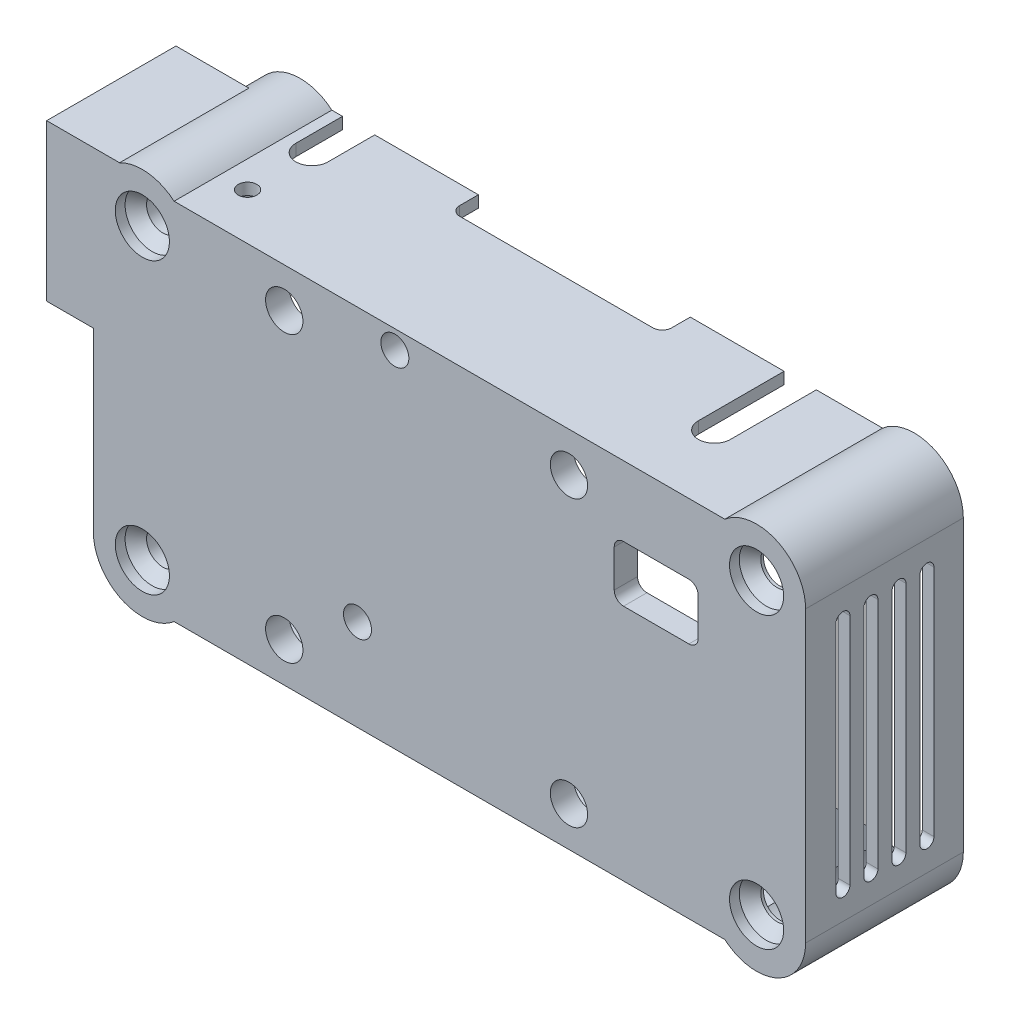
SolidWorks part; units mm, degrees
ref_plane "Front Plane" through (0, 0, 0) normal (0, 0, 1) x (1, 0, 0)
ref_plane "Top Plane" through (0, 0, 0) normal (0, 1, 0) x (1, 0, 0)
ref_plane "Right Plane" through (0, 0, 0) normal (1, 0, 0) x (0, 0, -1)
sketch "Sketch1" plane through (0, 0, 0) normal (0, 0, 1) x (1, 0, 0)
  line L0 (-29.7106, 19.8451) -> (30.4992, 19.8451)
  line L1 (-36.2557, 17.3451) -> (-36.2557, -13.6549)
  line L2 (-29.7106, -16.1549) -> (30.4992, -16.1549)
  line L3 (37.0443, 17.3451) -> (37.0443, -13.6549)
  circle A1 centre (-32.5057, 17.3451) radius 3.75
  arc A2 (-29.7106, 19.8451) -> (-36.2557, 17.3451) centre (-32.5057, 17.3451) ccw construction
  circle A3 centre (-32.5057, 17.3451) radius 1.75
  circle A4 centre (-32.5057, 17.3451) radius 1.75 construction
  circle A8 centre (-32.5057, -13.6549) radius 1.75
  circle A9 centre (-32.5057, -13.6549) radius 1.75 construction
  circle A10 centre (-32.5057, -13.6549) radius 3.75
  arc A11 (-36.2557, -13.6549) -> (-29.7106, -16.1549) centre (-32.5057, -13.6549) ccw construction
  circle A12 centre (33.2943, 17.3451) radius 3.75
  circle A14 centre (33.2943, 17.3451) radius 1.75
  circle A16 centre (33.2943, -13.6549) radius 3.75
  circle A18 centre (33.2943, -13.6549) radius 1.75
  circle A20 centre (33.2943, -13.6549) radius 1.75 construction
  circle A21 centre (33.2943, 17.3451) radius 1.75 construction
  arc A22 (37.0443, 17.3451) -> (30.1222, 15.3451) centre (33.2943, 17.3451) ccw construction
extrude "Boss-Extrude1" add sketch "Sketch1" along normal blind 2.5 contours A16 L3 A12 L0 A1 L1 A10 L2 | A1 A3 | A10 A8 | A12 A14 | A16 A18 region at (0.3943, 1.8451, 0) region at (-29.1016, 18.6453, 0) region at (34.5945, 20.7492, 0) region at (-32.5057, -10.011, 0) region at (34.5945, -17.059, 0)
sketch "Sketch2" plane through (0, 0, 2.5) normal (0, 0, 1) x (1, 0, 0)
  line L0 (-37.7557, 17.3451) -> (-37.7557, -13.6549)
  line L1 (-29.1053, -17.6549) -> (29.8939, -17.6549)
  line L2 (38.5443, -13.6549) -> (38.5443, 17.3451)
  line L3 (29.8939, 21.3451) -> (-29.1053, 21.3451)
  line L4 (-29.7106, -16.1549) -> (30.4992, -16.1549)
  line L5 (37.0443, -13.6549) -> (37.0443, 17.3451)
  line L6 (30.4992, 19.8451) -> (-29.7106, 19.8451)
  line L7 (-36.2557, 17.3451) -> (-36.2557, -13.6549)
  line L8 (-29.7106, -16.1549) -> (30.4992, -16.1549)
  line L9 (37.0443, -13.6549) -> (37.0443, 17.3451)
  line L10 (30.4992, 19.8451) -> (-29.7106, 19.8451)
  line L11 (-36.2557, 17.3451) -> (-36.2557, -13.6549)
  arc A0 (-29.1053, 21.3451) -> (-37.7557, 17.3451) centre (-32.5057, 17.3451) ccw
  arc A1 (-37.7557, -13.6549) -> (-29.1053, -17.6549) centre (-32.5057, -13.6549) ccw
  arc A2 (29.8939, -17.6549) -> (38.5443, -13.6549) centre (33.2943, -13.6549) ccw
  arc A3 (38.5443, 17.3451) -> (29.8939, 21.3451) centre (33.2943, 17.3451) ccw
  arc A4 (30.4992, -16.1549) -> (37.0443, -13.6549) centre (33.2943, -13.6549) ccw
  arc A5 (37.0443, 17.3451) -> (30.4992, 19.8451) centre (33.2943, 17.3451) ccw
  arc A6 (-29.7106, 19.8451) -> (-36.2557, 17.3451) centre (-32.5057, 17.3451) ccw
  arc A7 (-36.2557, -13.6549) -> (-29.7106, -16.1549) centre (-32.5057, -13.6549) ccw
  arc A8 (30.4992, -16.1549) -> (37.0443, -13.6549) centre (33.2943, -13.6549) ccw
  arc A9 (37.0443, 17.3451) -> (30.4992, 19.8451) centre (33.2943, 17.3451) ccw
  arc A10 (-29.7106, 19.8451) -> (-36.2557, 17.3451) centre (-32.5057, 17.3451) ccw
  arc A11 (-36.2557, -13.6549) -> (-29.7106, -16.1549) centre (-32.5057, -13.6549) ccw
  dimension "D1" = 0
  dimension "D2" = 1.5
extrude "Boss-Extrude2" add sketch "Sketch2" against normal up to surface (2.5 mm away) up to face at (0.3943, 1.8451, 0)
sketch "Sketch3" plane through (0, 0, 0) normal (0, 0, -1) x (-1, 0, 0)
  line L1 (29.601, 20.0951) -> (-30.3896, 20.0951)
  line L2 (-37.2943, 17.3451) -> (-37.2943, -13.6549)
  line L3 (-30.3896, -16.4049) -> (29.601, -16.4049)
  line L4 (29.1053, 21.3451) -> (-29.8939, 21.3451)
  line L5 (-38.5443, 17.3451) -> (-38.5443, -13.6549)
  line L6 (-29.8939, -17.6549) -> (29.1053, -17.6549)
  line L7 (37.7557, -13.6549) -> (37.7557, 17.3451)
  line L8 (29.1053, 21.3451) -> (-29.8939, 21.3451)
  line L9 (-38.5443, 17.3451) -> (-38.5443, -13.6549)
  line L10 (-29.8939, -17.6549) -> (29.1053, -17.6549)
  line L11 (37.7557, -13.6549) -> (37.7557, 17.3451)
  line L12 (36.5057, -13.6549) -> (36.5057, 17.3451)
  arc A1 (-30.3896, 20.0951) -> (-37.2943, 17.3451) centre (-33.2943, 17.3451) ccw
  arc A2 (-37.2943, -13.6549) -> (-30.3896, -16.4049) centre (-33.2943, -13.6549) ccw
  arc A3 (29.601, -16.4049) -> (36.5057, -13.6549) centre (32.5057, -13.6549) ccw
  arc A4 (37.7557, 17.3451) -> (29.1053, 21.3451) centre (32.5057, 17.3451) ccw
  arc A5 (-29.8939, 21.3451) -> (-38.5443, 17.3451) centre (-33.2943, 17.3451) ccw
  arc A6 (-38.5443, -13.6549) -> (-29.8939, -17.6549) centre (-33.2943, -13.6549) ccw
  arc A7 (29.1053, -17.6549) -> (37.7557, -13.6549) centre (32.5057, -13.6549) ccw
  arc A8 (37.7557, 17.3451) -> (29.1053, 21.3451) centre (32.5057, 17.3451) ccw
  arc A9 (-29.8939, 21.3451) -> (-38.5443, 17.3451) centre (-33.2943, 17.3451) ccw
  arc A10 (-38.5443, -13.6549) -> (-29.8939, -17.6549) centre (-33.2943, -13.6549) ccw
  arc A11 (29.1053, -17.6549) -> (37.7557, -13.6549) centre (32.5057, -13.6549) ccw
  arc A12 (36.5057, 17.3451) -> (29.601, 20.0951) centre (32.5057, 17.3451) ccw
  dimension "D1" = 0
  dimension "D2" = 1.25
extrude "Boss-Extrude3" add sketch "Sketch3" along normal up to surface (14.4 mm away)
sketch "Sketch8" plane through (0, 0, 0) normal (0, 0, -1) x (-1, 0, 0)
  line L0 (37.7557, 17.3451) -> (37.7557, -13.6549)
  line L1 (29.1053, 21.3451) -> (29.1053, -17.6549)
  circle A0 centre (32.5057, 17.3451) radius 5.25
  arc A1 (37.7557, 17.3451) -> (29.1053, 21.3451) centre (32.5057, 17.3451) ccw construction
  circle A2 centre (32.5057, 17.3451) radius 1.75
  circle A3 centre (32.5057, 17.3451) radius 1.75 construction
  circle A4 centre (32.5057, -13.6549) radius 5.25
  arc A5 (29.1053, -17.6549) -> (37.7557, -13.6549) centre (32.5057, -13.6549) ccw construction
  circle A6 centre (32.5057, -13.6549) radius 1.75
  circle A7 centre (32.5057, -13.6549) radius 1.75 construction
  circle M3 centre (32.5057, 17.3451) radius 1.75
  circle M4 centre (32.5057, -13.6549) radius 1.75
  arc M5 (29.601, -16.4049) -> (36.5057, -13.6549) centre (32.5057, -13.6549) ccw
  line M6 (36.5057, -13.6549) -> (36.5057, 17.3451)
  arc M7 (36.5057, 17.3451) -> (29.601, 20.0951) centre (32.5057, 17.3451) ccw
  line M8 (29.601, 20.0951) -> (-30.3896, 20.0951)
  line M12 (-30.3896, -16.4049) -> (29.601, -16.4049)
extrude "Boss-Extrude4" add sketch "Sketch8" along normal up to surface (6.75 mm away) contours L1 A0 M6 M7 M8 M3 | A4 A0 L1 M6 | A4 L1 M6 M12 M5 M4 region at (-32.835, 1.8451, 0) region at (-32.9201, 12.2303, 0) region at (-36.3872, -11.9547, 0)
sketch "Sketch4" plane through (-37.7557, 0, 0) normal (-1, 0, 0) x (0, 0, 1)
  line L12 (-11.9, -11.8549) -> (-3.3, -11.8549)
  line L13 (-3.3, -11.8549) -> (-3.3, 1.2216)
  line L14 (-3.3, 1.2216) -> (-6.0107, 4.2451)
  line L15 (-6.0107, 4.2451) -> (-9.1893, 4.2451)
  line L16 (-9.1893, 4.2451) -> (-11.9, 1.2216)
  line L17 (-11.9, 1.2216) -> (-11.9, -11.8549)
  line L18 (-11.9, -11.8549) -> (-3.3, -11.8549)
  line L19 (-3.3, -11.8549) -> (-3.3, 1.2216)
  line L20 (-3.3, 1.2216) -> (-6.0107, 4.2451)
  line L21 (-6.0107, 4.2451) -> (-9.1893, 4.2451)
  line L22 (-9.1893, 4.2451) -> (-11.9, 1.2216)
  line L23 (-11.9, 1.2216) -> (-11.9, -11.8549)
  dimension "D1" = 0.2
extrude "Cut-Extrude1" cut sketch "Sketch4" against normal up to next
sketch "Sketch5" plane through (0, 21.3451, 0) normal (0, 1, 0) x (1, 0, 0)
  line L0 (-27.9607, 9.4) -> (-27.9607, 14.4)
  line L1 (-29.1053, 14.4) -> (29.8939, 14.4) construction
  line L2 (-24.5107, 9.4) -> (-24.5107, 14.4)
  line L3 (-24.5107, 14.4) -> (-27.9607, 14.4)
  line L4 (19.3445, 5.2047) -> (19.3445, 14.4)
  line L5 (22.7945, 5.2047) -> (22.7945, 14.4)
  circle A1 centre (21.0695, 5.2047) radius 1.725
  circle A2 centre (-26.2357, 9.4) radius 1.725
  circle A3 centre (-26.2357, 9.4) radius 1.725
  circle A4 centre (21.0695, 5.2047) radius 0.95 construction
  line M3 (29.8939, 14.4) -> (-29.1053, 14.4)
  dimension "D1" = 0.5
extrude "Cut-Extrude2" cut sketch "Sketch5" against normal up to next contours A3 | A3 L2 L0 M3 | A1 L5 L4 M3 | A1 region at (21.0695, 21.3451, -10.4703) region at (-26.2357, 21.3451, -12.5571) region at (-26.2357, 21.3451, -9.4) region at (21.0695, 21.3451, -5.2047)
sketch "Sketch6" plane through (0, 21.3451, 0) normal (0, 1, 0) x (1, 0, 0)
  line L0 (-26.2357, 7.675) -> (-26.2357, -2.5) construction
  line L1 (29.8939, -2.5) -> (-29.1053, -2.5) construction
  arc A0 (-27.9607, 9.4) -> (-24.5107, 9.4) centre (-26.2357, 9.4) ccw construction
  circle A1 centre (-26.2357, 2.5) radius 1
  dimension "D1" = 2
  dimension "D2" = 5
extrude "Cut-Extrude3" cut sketch "Sketch6" against normal through all
sketch "Sketch7" plane through (0, 0, 2.5) normal (0, 0, 1) x (1, 0, 0)
  line L1 (27.0443, 7.8451) -> (18.0443, 7.8451)
  line L2 (27.0443, 7.8451) -> (27.0443, 13.8451)
  line L3 (27.0443, 13.8451) -> (18.0443, 13.8451)
  line L4 (18.0443, 7.8451) -> (18.0443, 13.8451)
  line L6 (38.5443, -13.6549) -> (38.5443, 17.3451) construction
  line L7 (29.8939, 21.3451) -> (-29.1053, 21.3451) construction
  line L8 (-3.2057, 19.3451) -> (-3.2057, 21.3451) construction
  line L9 (-7.7057, 19.3451) -> (-7.7057, 21.3451) construction
  line L10 (-3.2057, 18.0451) -> (-3.2057, 19.8451) construction
  line L11 (-7.7057, 18.0451) -> (-7.7057, 19.8451) construction
  circle A0 centre (-9.4557, -7.8549) radius 1.5
  circle A1 centre (-5.4557, 19.3451) radius 2.25
  circle A2 centre (-9.4557, -7.8549) radius 0.875 construction
  circle A3 centre (-5.4557, 19.3451) radius 1.5
  dimension "D5" = 2
  dimension "D6" = 3
  dimension "D1" = 11.5
  dimension "D2" = 7.5
  dimension "D3" = 6
  dimension "D4" = 9
extrude "Cut-Extrude4" cut sketch "Sketch7" against normal up to next contours L4 L1 L2 L3 | A3 | A0 region at (22.5443, 10.8451, 2.5) region at (-9.4557, -7.8549, 2.5) region at (-5.4557, 19.3451, 2.5)
sketch "Sketch9" plane through (0, 0, 2.5) normal (0, 0, 1) x (1, 0, 0)
  circle A0 centre (-32.5057, 17.3451) radius 2.9
  circle A1 centre (33.2943, 17.3451) radius 2.9
  circle A2 centre (33.2943, -13.6549) radius 2.9
  circle A3 centre (-32.5057, -13.6549) radius 2.9
  dimension "D1" = 5.8
extrude "Cut-Extrude5" cut sketch "Sketch9" against normal blind 0.2
chamfer "Chamfer1" distance 2 angle 45 4 edges at (35.0443, -13.6549, 2.3) (35.0443, 17.3451, 2.3) (-30.7557, -13.6549, 2.3) (-30.7557, 17.3451, 2.3)
sketch "Sketch10" plane through (0, 21.3451, 0) normal (0, 1, 0) x (1, 0, 0)
  line L0 (-24.5107, 14.4) -> (19.3445, 14.4) construction
  line L1 (9.2943, 14.4) -> (4.6943, 14.4)
  line L2 (9.2943, 14.4) -> (9.2943, 11.4)
  line L3 (9.2943, 11.4) -> (4.6943, 11.4)
  line L4 (4.6943, 14.4) -> (4.6943, 11.4)
  line L5 (9.2943, 13.7) -> (9.2943, 11.9) construction
  line L6 (4.6943, 13.7) -> (4.6943, 11.9) construction
  line L7 (-8.8057, 13.7) -> (-8.8057, 11.9) construction
  line L8 (-8.8057, 14.4) -> (-13.4057, 14.4)
  line L9 (-8.8057, 14.4) -> (-8.8057, 11.4)
  line L10 (-8.8057, 11.4) -> (-13.4057, 11.4)
  line L11 (-13.4057, 14.4) -> (-13.4057, 11.4)
  line L12 (-13.4057, 13.7) -> (-13.4057, 11.9) construction
  line L14 (-8.8057, 14.4) -> (4.6943, 14.4)
  line L15 (-8.8057, 14.4) -> (-8.8057, 11.4)
  line L16 (-8.8057, 11.4) -> (4.6943, 11.4)
  line L17 (4.6943, 14.4) -> (4.6943, 11.4)
  line M23 (19.3445, 14.4) -> (-24.5107, 14.4)
  dimension "D1" = 3
extrude "Cut-Extrude6" cut sketch "Sketch10" against normal through all contours L11 L10 L9 M23 | L9 L16 L4 M23 | L4 L3 L2 M23 region at (6.9943, 21.3451, -12.9) region at (-2.0557, 21.3451, -12.9) region at (-11.1057, 21.3451, -12.9)
fillet "Fillet1" radius 1 8 edges at (27.0443, 13.8451, 1.25) (27.0443, 7.8451, 1.25) (18.0443, 7.8451, 1.25) (18.0443, 13.8451, 1.25) (9.2943, 20.7201, -11.4) (9.2943, -17.0299, -11.4) (-13.4057, -17.0299, -11.4) (-13.4057, 20.7201, -11.4)
sketch "Sketch11" plane through (0, 0, -3.3) normal (0, 0, -1) x (-1, 0, 0)
  line L0 (29.1053, -5.3166) -> (36.5057, -5.3166) construction
  line L1 (29.1053, 1.2216) -> (29.1053, -11.8549) construction
  line L2 (36.5057, -13.6549) -> (36.5057, 17.3451) construction
  line L3 (29.1053, 1.2216) -> (37.7557, 1.2216) construction
  line L4 (32.5555, 1.2216) -> (33.0555, 1.2216)
  line L5 (32.5555, 1.2216) -> (32.5555, -11.8549)
  line L6 (32.5555, -11.8549) -> (33.0555, -11.8549)
  line L7 (33.0555, 1.2216) -> (33.0555, -11.8549)
  line L8 (32.5555, 1.2216) -> (33.0555, -11.8549) construction
  line L9 (32.5555, -11.8549) -> (33.0555, 1.2216) construction
  point P6 (32.8055, -5.3166)
  dimension "D1" = 0.5
extrude "Boss-Extrude5" add sketch "Sketch11" along normal blind 0.25
sketch "Sketch12" plane through (0, 0, 2.5) normal (0, 0, 1) x (1, 0, 0)
  circle A0 centre (-17.3057, 17.0951) radius 2
  circle A1 centre (13.1943, 17.0951) radius 2
  circle A2 centre (13.1943, -13.4049) radius 2
  circle A3 centre (-17.3057, -13.4049) radius 2
  circle A4 centre (-17.3057, 17.0951) radius 1.5 construction
  circle A5 centre (-17.3057, -13.4049) radius 1.5 construction
  circle A6 centre (13.1943, -13.4049) radius 1.5 construction
  circle A7 centre (13.1943, 17.0951) radius 1.5 construction
  dimension "D1" = 4
extrude "Cut-Extrude7" cut sketch "Sketch12" against normal up to next
sketch "Sketch13" plane through (38.5443, 0, 0) normal (1, 0, 0) x (0, 0, -1)
  line L0 (1.5, 22.5951) -> (1.5, -18.9049) construction
  line L1 (14.4, 22.5951) -> (-2.5, 22.5951) construction
  line L2 (-2.5, -18.9049) -> (14.4, -18.9049) construction
  line L3 (-2.5, 22.5951) -> (-2.5, 17.3451) construction
  line L4 (-2.5, 1.8451) -> (14.4, 1.8451) construction
  line L5 (-2.5, -13.6549) -> (-2.5, 17.3451) construction
  line L6 (14.4, 17.3451) -> (14.4, -13.6549) construction
  line L7 (1.5, 14.3451) -> (1.5, -10.6549) construction
  line L8 (2.25, 14.3451) -> (2.25, -10.6549)
  line L9 (0.75, 14.3451) -> (0.75, -10.6549)
  line L10 (4.5, 14.3451) -> (4.5, -10.6549) construction
  line L11 (5.25, 14.3451) -> (5.25, -10.6549)
  line L12 (3.75, 14.3451) -> (3.75, -10.6549)
  line L13 (7.5, 14.3451) -> (7.5, -10.6549) construction
  line L14 (8.25, 14.3451) -> (8.25, -10.6549)
  line L15 (6.75, 14.3451) -> (6.75, -10.6549)
  line L16 (10.5, 14.3451) -> (10.5, -10.6549) construction
  line L17 (11.25, 14.3451) -> (11.25, -10.6549)
  line L18 (9.75, 14.3451) -> (9.75, -10.6549)
  arc A0 (2.25, 14.3451) -> (0.75, 14.3451) centre (1.5, 14.3451) ccw
  arc A1 (0.75, -10.6549) -> (2.25, -10.6549) centre (1.5, -10.6549) ccw
  arc A2 (5.25, 14.3451) -> (3.75, 14.3451) centre (4.5, 14.3451) ccw
  arc A3 (3.75, -10.6549) -> (5.25, -10.6549) centre (4.5, -10.6549) ccw
  arc A4 (8.25, 14.3451) -> (6.75, 14.3451) centre (7.5, 14.3451) ccw
  arc A5 (6.75, -10.6549) -> (8.25, -10.6549) centre (7.5, -10.6549) ccw
  arc A6 (11.25, 14.3451) -> (9.75, 14.3451) centre (10.5, 14.3451) ccw
  arc A7 (9.75, -10.6549) -> (11.25, -10.6549) centre (10.5, -10.6549) ccw
  point P17 (1.5, 1.8451)
  point P25 (4.5, 1.8451)
  point P32 (7.5, 1.8451)
  point P39 (10.5, 1.8451)
  dimension "D1" = 4
  dimension "D2" = 25
  dimension "D3" = 1.5
  dimension "D5" = 3
  dimension "D4" = 4
extrude "Cut-Extrude8" cut sketch "Sketch13" against normal up to surface (1.25 mm away) up to face at (37.2943, 1.8451, -7.2)
sketch "Sketch14" plane through (-37.7557, 0, 0) normal (-1, 0, 0) x (0, 0, 1)
  line L0 (-7.6, -11.8549) -> (-7.6, 17.3451) construction
  line L1 (-11.9, -11.8549) -> (-3.3, -11.8549) construction
  line L2 (-14.4, 17.3451) -> (2.5, 17.3451) construction
  line L3 (-7.6, 20.4951) -> (-7.6, 6.7451) construction
  line L4 (-9.85, 20.4951) -> (-5.35, 20.4951)
  line L5 (-9.85, 20.4951) -> (-9.85, 6.7451)
  line L6 (-9.85, 6.7451) -> (-5.35, 6.7451)
  line L7 (-5.35, 20.4951) -> (-5.35, 6.7451)
  line L8 (-6.0107, 4.2451) -> (-9.1893, 4.2451) construction
  line L9 (-9.85, 13.6201) -> (-5.35, 13.6201) construction
  line L10 (-5.35, 17.5701) -> (-4.15, 17.5701)
  line L11 (-5.35, 17.5701) -> (-5.35, 19.0701)
  line L12 (-5.35, 19.0701) -> (-4.15, 19.0701)
  line L13 (-4.15, 17.5701) -> (-4.15, 19.0701)
  line L14 (-4.15, 18.3201) -> (-5.35, 18.3201) construction
  line L15 (-5.35, 8.1701) -> (-4.15, 8.1701)
  line L16 (-4.15, 9.6701) -> (-4.15, 8.1701)
  line L17 (-5.35, 9.6701) -> (-4.15, 9.6701)
  line M21 (2.5, 17.3451) -> (-14.4, 17.3451)
  dimension "D1" = 4.5
  dimension "D2" = 13.75
  dimension "D3" = 2.5
  dimension "D4" = 1.5
  dimension "D5" = 1.2
  dimension "D6" = 4.7
extrude "Cut-Extrude9" cut sketch "Sketch14" against normal offset from surface (0.75 mm away) 0.5 contours L7 L4 L5 M21 | L7 L5 L6 M21 | L10 L13 L12 L7 | L17 L7 L15 L16 region at (-37.7557, 18.9201, -7.6) region at (-37.7557, 12.0451, -7.6) region at (-37.7557, 18.3201, -4.75) region at (-37.7557, 8.9201, -4.75) up to face at (-36.5057, -0.7353, -9.8655)
sketch "Sketch15" plane through (-37.7557, 0, 0) normal (1, 0, 0) x (0, 0, -1)
  line L0 (9.85, 13.6201) -> (11.35, 13.6201) construction
  line L1 (11.35, 21.9951) -> (2.65, 21.9951)
  line L2 (11.35, 21.9951) -> (11.35, 5.2451)
  line L3 (11.35, 5.2451) -> (2.65, 5.2451)
  line L4 (2.65, 21.9951) -> (2.65, 5.2451)
  line L5 (9.85, 20.4951) -> (9.85, 6.7451) construction
  line L6 (-2.5, 17.3451) -> (-2.5, -13.6549) construction
  line L7 (2.65, 21.9951) -> (-2.5, 21.9951)
  line L8 (7.6, 6.7451) -> (7.6, 5.2451) construction
  line L9 (7.6, -11.8549) -> (7.6, 17.3451) construction
  line L10 (4.15, 18.3201) -> (2.65, 18.3201) construction
  line L11 (2.65, 21.9951) -> (2.65, 5.2451)
  line L12 (9.85, 20.0493) -> (5.35, 20.0493)
  line L13 (9.85, 6.7451) -> (9.85, 20.0493)
  line L14 (9.85, 20.0493) -> (5.35, 20.0493)
  line L15 (5.35, 6.7451) -> (9.85, 6.7451)
  line L16 (5.35, 6.7451) -> (9.85, 6.7451)
  line L17 (5.35, 8.1701) -> (5.35, 6.7451)
  line L18 (5.35, 8.1701) -> (5.35, 6.7451)
  line L19 (5.35, 17.5701) -> (5.35, 9.6701)
  line L20 (4.15, 17.5701) -> (5.35, 17.5701)
  line L21 (4.15, 19.0701) -> (4.15, 17.5701)
  line L22 (5.35, 19.0701) -> (4.15, 19.0701)
  line L23 (5.35, 20.0493) -> (5.35, 19.0701)
  line L24 (4.15, 8.1701) -> (5.35, 8.1701)
  line L25 (9.85, 6.7451) -> (9.85, 20.0493)
  line L26 (4.15, 8.1701) -> (5.35, 8.1701)
  line L27 (4.15, 9.6701) -> (4.15, 8.1701)
  line L28 (4.15, 9.6701) -> (4.15, 8.1701)
  line L29 (5.35, 9.6701) -> (4.15, 9.6701)
  line L30 (5.35, 9.6701) -> (4.15, 9.6701)
  line L31 (5.35, 17.5701) -> (5.35, 9.6701)
  line L32 (4.15, 17.5701) -> (5.35, 17.5701)
  line L33 (4.15, 19.0701) -> (4.15, 17.5701)
  line L34 (5.35, 19.0701) -> (4.15, 19.0701)
  line L35 (5.35, 20.0493) -> (5.35, 19.0701)
  line L36 (2.65, 5.2451) -> (-2.5, 5.2451)
  line L37 (-2.5, 21.9951) -> (-2.5, 5.2451)
  point P19 (11.35, 13.6201)
  line M70 (-2.5, 17.3451) -> (5.35, 17.3451)
  line M71 (5.35, 17.3451) -> (5.35, 9.6701)
  line M72 (5.35, 9.6701) -> (4.15, 9.6701)
  line M73 (4.15, 9.6701) -> (4.15, 8.1701)
  line M74 (4.15, 8.1701) -> (5.35, 8.1701)
  line M75 (5.35, 8.1701) -> (5.35, 6.7451)
  line M76 (5.35, 6.7451) -> (9.85, 6.7451)
  line M77 (9.85, 6.7451) -> (9.85, 17.3451)
  line M78 (9.85, 17.3451) -> (14.4, 17.3451)
  line M81 (-2.5, -13.6549) -> (-2.5, 17.3451)
  dimension "D2" = 1.5
  dimension "D1" = 0
extrude "Boss-Extrude9" add sketch "Sketch15" along normal up to next from offset 5 contours L14 L35 L34 L33 L32 L31 L4 L1 L2 L25 M70 M78 | L4 L2 L3 M70 M71 M72 M73 M74 M75 M76 M77 M78 | L4 L36 M81 M70 | L37 L7 L4 M70 region at (-37.7557, 20.2088, -6.8772) region at (-37.7557, 19.6701, -0.075) region at (-37.7557, 11.2951, -11.201) region at (-37.7557, 11.2951, -0.075) offset against normal yes
sketch "Sketch18" [suppressed] plane through (0, 21.9951, 0) normal (0, 1, 0) x (1, 0, 0)
  line L0 (-37.7557, -2.5) -> (-42.7557, 2.65)
  line L1 (-42.7557, 11.35) -> (-42.7557, -2.5) construction
  line L2 (-42.7557, 2.65) -> (-42.7557, -2.5)
  line L3 (-42.7557, -2.5) -> (-37.7557, -2.5)
  line L4 (-34.9429, -2.5) -> (-42.7557, -2.5) construction
  line M3 (-42.7557, -2.5) -> (-34.9429, -2.5)
  line M6 (-42.7557, 11.35) -> (-42.7557, -2.5)
  dimension "D1" = 1.5
extrude "Cut-Extrude11" [suppressed] cut sketch "Sketch18" against normal up to surface (16.75 mm away) contours L0 M3 M6 up to face at (-40.2557, 5.2451, -4.425)
